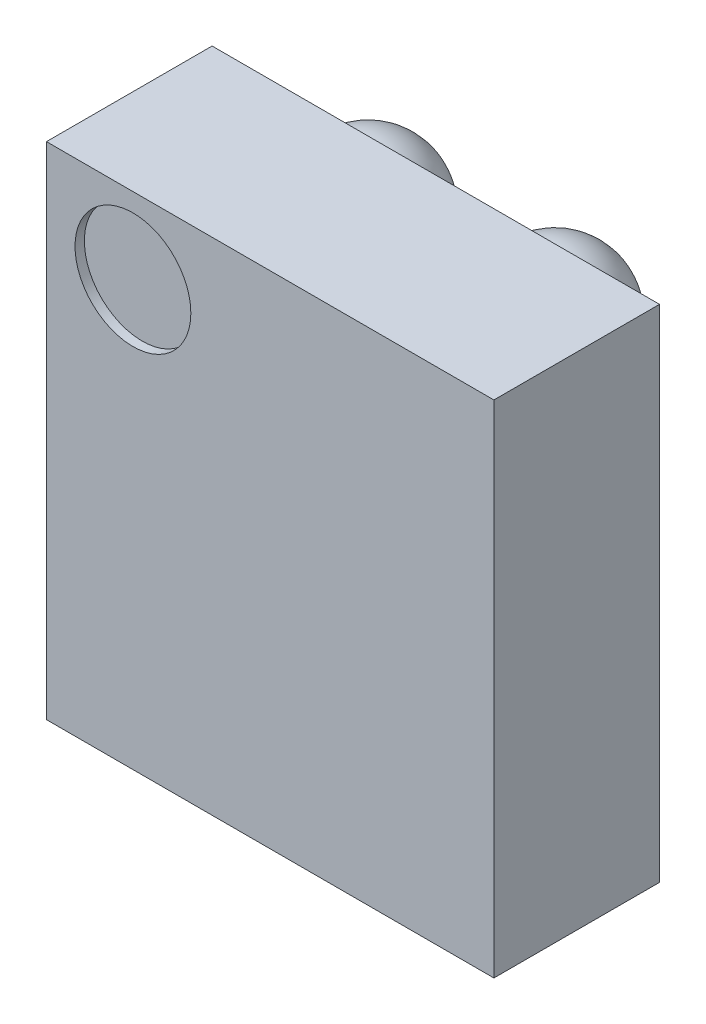
SolidWorks part; units mm, degrees
ref_plane "Front Plane" through (0, 0, 0) normal (0, 0, 1) x (1, 0, 0)
ref_plane "Top Plane" through (0, 0, 0) normal (0, 1, 0) x (1, 0, 0)
ref_plane "Right Plane" through (0, 0, 0) normal (1, 0, 0) x (0, 0, -1)
sketch "Sketch1" plane through (0, 0, 0) normal (0, 0, 1) x (1, 0, 0)
  line L1 (-0.4795, -0.5365) -> (0.4795, -0.5365)
  line L2 (-0.4795, -0.5365) -> (-0.4795, 0.5365)
  line L3 (-0.4795, 0.5365) -> (0.4795, 0.5365)
  line L4 (0.4795, -0.5365) -> (0.4795, 0.5365)
  line L5 (-0.4795, -0.5365) -> (0.4795, 0.5365) construction
  line L6 (-0.4795, 0.5365) -> (0.4795, -0.5365) construction
  point P0 (0, 0)
  dimension "D1" = 0.959
  dimension "D2" = 1.073
extrude "Boss-Extrude1" add sketch "Sketch1" along normal blind 0.355 from offset 0.19 contours L3 L4 L1 L2
sketch "Sketch2" plane through (0, 0, 0) normal (0, 1, 0) x (1, 0, 0)
  line L0 (0, 0) -> (0, -0.27)
  arc A0 (0, -0.27) -> (0, 0) centre (0, -0.135) ccw
  dimension "D1" = 0.27
revolve "Revolve1" add sketch "Sketch2" angle 360 about L0
pattern_linear "LPattern1" count 2 spacing 0.3465 along (0, 1, 0) count 2 spacing 0.2 along (1, 0, 0) skipping (0, 1), (1, 0) of "Revolve1"
pattern_linear "LPattern2" count 2 spacing 0.693 along (0, -1, 0) count 2 spacing 0.4 along (-1, 0, 0) of face at (0.0767, 0.3465, 0.19)
sketch "Sketch3" plane through (0, 0, 0.545) normal (0, 0, 1) x (1, 0, 0)
  circle A0 centre (-0.2942, 0.3729) radius 0.1241
  point P2 (-0.2942, 0.3729)
extrude "Cut-Extrude3" cut sketch "Sketch3" against normal blind 0.02 contours A0
